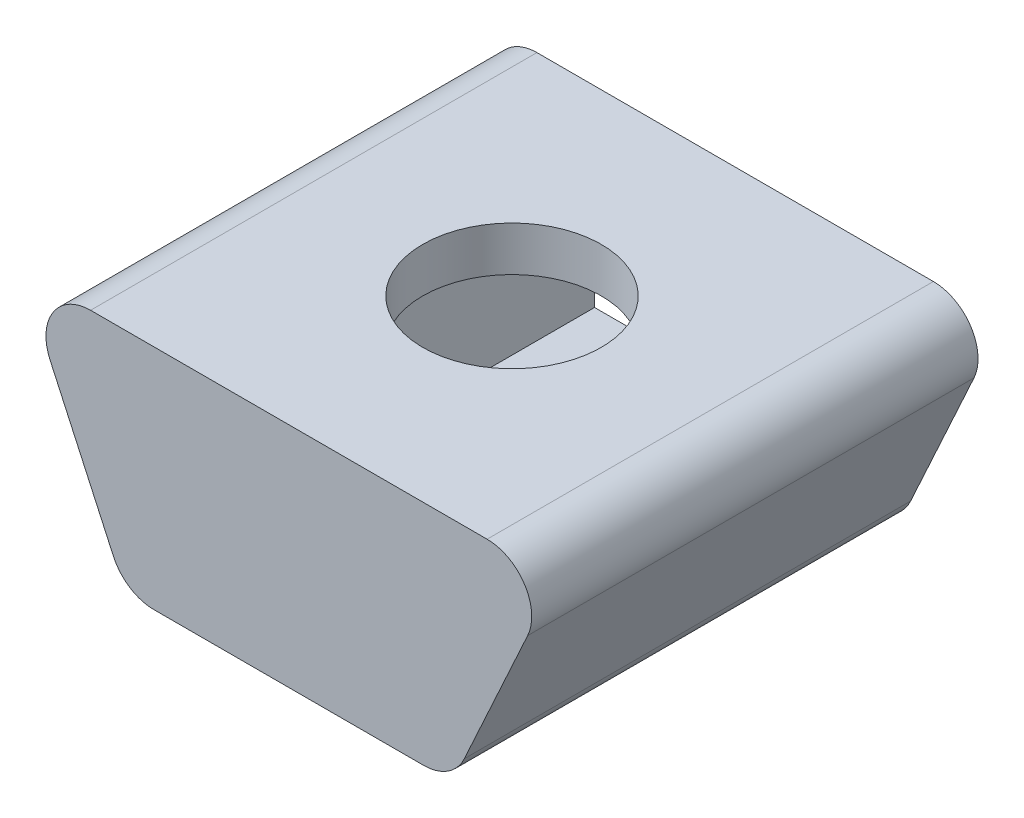
SolidWorks part; units mm, degrees
ref_plane "Front Plane" through (0, 0, 0) normal (0, 0, 1) x (1, 0, 0)
ref_plane "Top Plane" through (0, 0, 0) normal (0, 1, 0) x (1, 0, 0)
ref_plane "Right Plane" through (0, 0, 0) normal (1, 0, 0) x (0, 0, -1)
sketch "Sketch1" plane through (0, 0, 0) normal (0, 0, 1) x (1, 0, 0)
  line L0 (-6, 2.65) -> (6, 2.65)
  line L1 (-3.15, -1.65) -> (3.15, -1.65)
  line L2 (-3.15, -1.65) -> (-3.15, 1.65)
  line L3 (-3.15, 1.65) -> (3.15, 1.65)
  line L4 (3.15, -1.65) -> (3.15, 1.65)
  line L5 (-3.15, -1.65) -> (3.15, 1.65) construction
  line L6 (-3.15, 1.65) -> (3.15, -1.65) construction
  line L7 (0, 2.65) -> (0, 0) construction
  line L8 (-6, 2.65) -> (-3.6634, -2.45)
  line L9 (-3.6634, -2.45) -> (3.6634, -2.45)
  line L10 (3.6634, -2.45) -> (6, 2.65)
  line L11 (0, 0) -> (0, -2.45) construction
  point P0 (0, 0)
  dimension "D1" = 6.3
  dimension "D2" = 3.3
  dimension "D3" = 12
  dimension "D4" = 1
  dimension "D5" = 0.8
  dimension "D6" = 0.8
extrude "Boss-Extrude1" add sketch "Sketch1" against normal blind 8
extrude "Boss-Extrude2" add sketch "Sketch1<2>" along normal blind 2 contours L0 L10 L9 L8
sketch "Sketch1<2>" plane through (0, 0, 0) normal (0, 0, 1) x (1, 0, 0) same geometry as "Sketch1"
sketch "Sketch2" plane through (0, 2.65, 0) normal (0, 1, 0) x (1, 0, 0)
  line L0 (0, -2) -> (0, 8) construction
  line L1 (-6, -2) -> (6, -2) construction
  line L2 (6, 8) -> (-6, 8) construction
  circle A0 centre (0, 3) radius 2
  dimension "D1" = 4
extrude "Cut-Extrude1" cut sketch "Sketch2" against normal up to surface (1 mm away) up to face at (0, 1.65, -4)
fillet "Fillet1" radius 1 4 edges at (-3.6634, -2.45, -3) (3.6634, -2.45, -3) (-6, 2.65, -3) (6, 2.65, -3)
